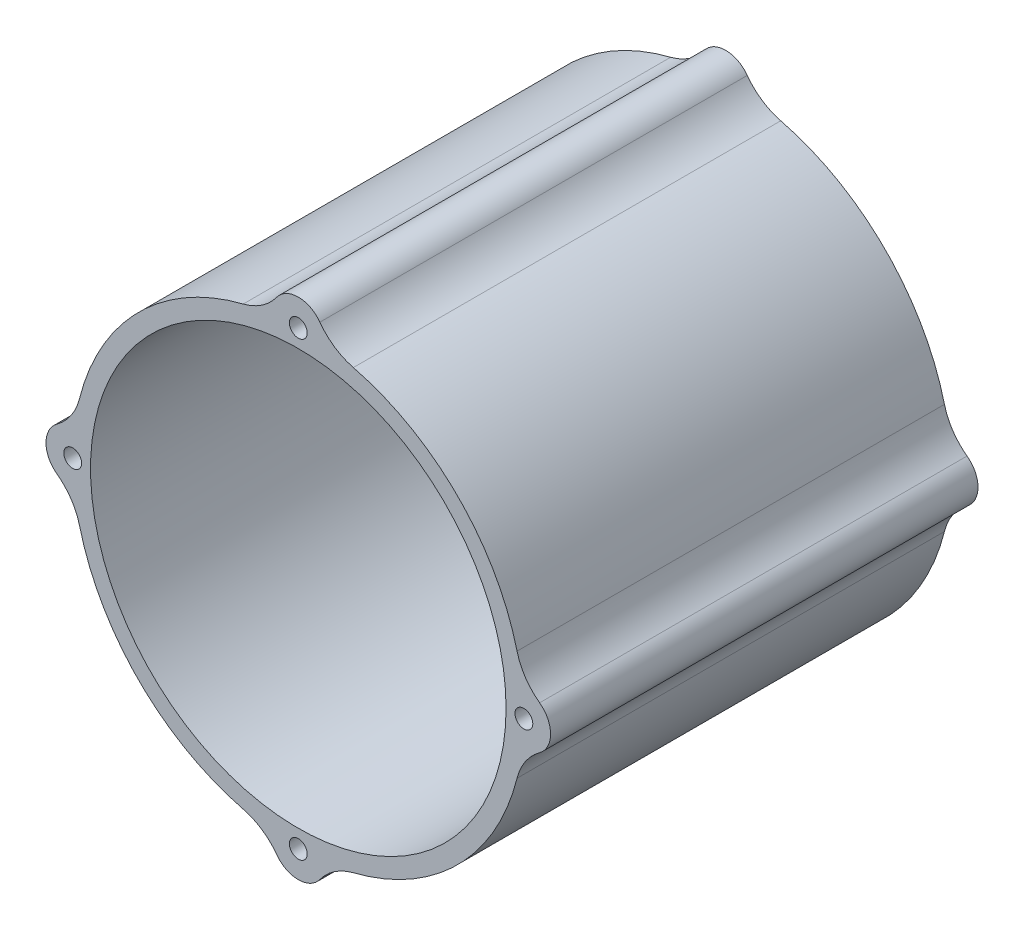
SolidWorks part; units mm, degrees
ref_plane "Ön Düzlem" through (0, 0, 0) normal (0, 0, 1) x (1, 0, 0)
ref_plane "Üst Düzlem" through (0, 0, 0) normal (0, 1, 0) x (1, 0, 0)
ref_plane "Sağ Düzlem" through (0, 0, 0) normal (1, 0, 0) x (0, 0, -1)
sketch "Çizim1" plane through (0, 0, 0) normal (0, 0, 1) x (1, 0, 0)
  circle A0 centre (0, 0) radius 35
  arc A1 (-36.8516, -9.2716) -> (-9.2716, -36.8516) centre (0, 0) ccw
  circle A6 centre (-38, 0) radius 1.5
  arc A7 (-40.6532, 3.6346) -> (-40.6532, -3.6346) centre (-38, 0) ccw
  circle A8 centre (0, 0) radius 38 construction
  arc A9 (-36.8516, -9.2716) -> (-40.6532, -3.6346) centre (-46.5493, -11.7115) ccw
  arc A10 (-36.8516, 9.2716) -> (-40.6532, 3.6346) centre (-46.5493, 11.7115) cw
  circle A11 centre (0, 38) radius 1.5
  arc A12 (3.6346, 40.6532) -> (-3.6346, 40.6532) centre (0, 38) ccw
  arc A13 (-9.2716, 36.8516) -> (-3.6346, 40.6532) centre (-11.7115, 46.5493) ccw
  arc A14 (9.2716, 36.8516) -> (3.6346, 40.6532) centre (11.7115, 46.5493) cw
  circle A15 centre (38, 0) radius 1.5
  arc A16 (40.6532, -3.6346) -> (40.6532, 3.6346) centre (38, 0) ccw
  arc A17 (36.8516, 9.2716) -> (40.6532, 3.6346) centre (46.5493, 11.7115) ccw
  arc A18 (36.8516, -9.2716) -> (40.6532, -3.6346) centre (46.5493, -11.7115) cw
  circle A19 centre (0, -38) radius 1.5
  arc A20 (-3.6346, -40.6532) -> (3.6346, -40.6532) centre (0, -38) ccw
  arc A21 (9.2716, -36.8516) -> (3.6346, -40.6532) centre (11.7115, -46.5493) ccw
  arc A22 (-9.2716, -36.8516) -> (-3.6346, -40.6532) centre (-11.7115, -46.5493) cw
  arc A23 (-9.2716, 36.8516) -> (-36.8516, 9.2716) centre (0, 0) ccw
  arc A24 (36.8516, 9.2716) -> (9.2716, 36.8516) centre (0, 0) ccw
  arc A25 (9.2716, -36.8516) -> (36.8516, -9.2716) centre (0, 0) ccw
  point P13 (-0.5295, 26.2002)
  point P14 (0, 0)
  point P16 (0, 0)
  point P41 (0, 0)
  dimension "D1" = 70
  dimension "D4" = 3
  dimension "D5" = 9
  dimension "D6" = 10
  dimension "38" = 38
  dimension "D2" = 3
  dimension "D7" = 4
extrude "Yükseklik-Ekstrüzyon1" add sketch "Çizim1" along normal blind 72
